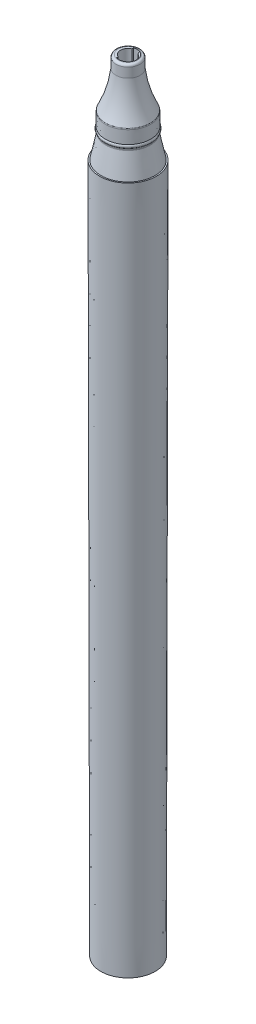
SolidWorks part; units mm, degrees
ref_plane "Plano frontal" through (0, 0, 0) normal (0, 0, 1) x (1, 0, 0)
ref_plane "Plano superior" through (0, 0, 0) normal (0, 1, 0) x (1, 0, 0)
ref_plane "Plano direito" through (0, 0, 0) normal (1, 0, 0) x (0, 0, -1)
sketch "Esboço1" plane through (0, 0, 0) normal (0, 0, 1) x (1, 0, 0)
  line L94 (3.75, 121.7) -> (3.7706, 119.7748) construction
  line L95 (4.275, 114.7) -> (4.5235, 0.7015)
  line L96 (3.8235, 0) -> (3.8021, 0)
  line L98 (2.01, 127.9) -> (2.01, 129.5)
  line L99 (1.61, 129.9) -> (1.5, 129.9)
  line L100 (3.825, 114.7) -> (4.275, 114.7)
  line L102 (0, 0) -> (0, 129.9) construction
  line L105 (2.3814, 122.73) -> (3.2071, 121.9043)
  line L110 (3.75, 121.7) -> (3.7706, 119.7748)
  line L117 (3.7852, 118.4178) -> (3.825, 114.7)
  line L119 (3.8235, 0) -> (3.8021, 0)
  line L123 (3.7764, 119.2315) -> (3.7852, 118.4178)
  line L124 (3.7764, 119.2315) -> (3.8229, 114.8979) construction
  line L152 (3.8021, 0.5) -> (3.8021, 0)
  line L153 (3.3527, 16.58) -> (3.2071, 121.9043)
  line L154 (3.4327, 11.1) -> (3.3677, 11.1)
  line L155 (3.4327, 8.5) -> (3.4327, 11.1)
  line L156 (3.3677, 8.5) -> (3.4327, 8.5)
  line L157 (3.3677, 5.8) -> (3.3677, 8.5)
  line L158 (3.4327, 5.8) -> (3.3677, 5.8)
  line L159 (3.4327, 3.2) -> (3.4327, 5.8)
  line L160 (3.3927, 3.2) -> (3.4327, 3.2)
  line L161 (3.3927, 0.5) -> (3.3927, 3.2)
  line L162 (3.3927, 0.5) -> (3.8021, 0.5)
  line L163 (3.3677, 11.1) -> (3.3527, 16.58)
  line L164 (33.3928, 114.7062) -> (34.2835, 114.7062)
  line L165 (31.5778, 127.9062) -> (31.5778, 129.5062)
  line L166 (31.1778, 129.9062) -> (31.0678, 129.9062)
  line L167 (29.5678, 129.9062) -> (29.5678, 114.7062) construction
  line L168 (29.5678, 0.0062) -> (29.5678, 129.9062) construction
  line L169 (32.0493, 122.6362) -> (32.7749, 121.9105)
  line L170 (33.3178, 121.7062) -> (33.3406, 119.5832)
  line L172 (31.0678, 129.9062) -> (31.0678, 127.9062)
  line L173 (34.0928, 0) -> (34.2835, 114.7062)
  line L174 (33.5193, 0.001) -> (34.0928, 0)
  line L175 (33.4928, 0.5062) -> (33.5193, 0.001)
  line L176 (32.8778, 16.5862) -> (32.7428, 114.2362)
  line L177 (32.9578, 11.1062) -> (32.8928, 11.1062)
  line L178 (32.9578, 8.5062) -> (32.9578, 11.1062)
  line L179 (32.8928, 8.5062) -> (32.9578, 8.5062)
  line L180 (32.8928, 5.8062) -> (32.8928, 8.5062)
  line L181 (32.9578, 5.8062) -> (32.8928, 5.8062)
  line L182 (32.9578, 3.2062) -> (32.9578, 5.8062)
  line L183 (32.9178, 3.2062) -> (32.9578, 3.2062)
  line L184 (32.9178, 0.5062) -> (32.9178, 3.2062)
  line L185 (32.9178, 0.5062) -> (33.4928, 0.5062)
  line L186 (32.8928, 11.1062) -> (32.8778, 16.5862)
  line L187 (56.8307, 127.9062) -> (56.8307, 129.5062)
  line L188 (56.4307, 129.9062) -> (56.3207, 129.9062)
  line L189 (54.8207, 129.9062) -> (54.8207, 114.7062) construction
  line L190 (54.8207, 0.0062) -> (54.8207, 129.9062) construction
  line L191 (57.3021, 122.6362) -> (58.0278, 121.9105)
  line L192 (58.5707, 121.7062) -> (58.5934, 119.5832)
  line L193 (56.3207, 129.9062) -> (56.3207, 127.9062)
  line L194 (59.3457, 0) -> (59.5364, 114.7062)
  line L195 (58.7722, 0.001) -> (59.3457, 0)
  line L196 (58.7457, 0.5062) -> (58.7722, 0.001)
  line L197 (58.1307, 16.5862) -> (57.9957, 114.2362)
  line L198 (58.2107, 11.1062) -> (58.1457, 11.1062)
  line L199 (58.2107, 8.5062) -> (58.2107, 11.1062)
  line L200 (58.1457, 8.5062) -> (58.2107, 8.5062)
  line L201 (58.1457, 5.8062) -> (58.1457, 8.5062)
  line L202 (58.2107, 5.8062) -> (58.1457, 5.8062)
  line L203 (58.2107, 3.2062) -> (58.2107, 5.8062)
  line L204 (58.1707, 3.2062) -> (58.2107, 3.2062)
  line L205 (58.1707, 0.5062) -> (58.1707, 3.2062)
  line L206 (58.1707, 0.5062) -> (58.7457, 0.5062)
  line L207 (58.1457, 11.1062) -> (58.1307, 16.5862)
  line L208 (58.4965, 118.7457) -> (59.091, 114.7062)
  line L209 (59.091, 114.7062) -> (59.5364, 114.7062)
  arc A9 (3.75, 121.7) -> (3.73, 121.9) centre (2.75, 121.701) ccw
  arc A10 (2.01, 127.9) -> (3.73, 121.9) centre (19.911, 129.7851) ccw
  arc A11 (2.01, 129.5) -> (1.61, 129.9) centre (1.61, 129.5) ccw
  arc A13 (3.7706, 119.7748) -> (3.7764, 119.2315) centre (3.48, 119.5) cw
  arc A14 (4.5235, 0.7015) -> (3.8235, 0) centre (3.8235, 0.7) cw
  arc A17 (33.3178, 121.7062) -> (33.2978, 121.9062) centre (32.3178, 121.7072) ccw
  arc A18 (31.5778, 127.9062) -> (33.2978, 121.9062) centre (49.4788, 129.7913) ccw
  arc A19 (31.5778, 129.5062) -> (31.1778, 129.9062) centre (31.1778, 129.5062) ccw
  arc A20 (31.9162, 122.8748) -> (32.0493, 122.6362) centre (32.4028, 122.9897) ccw
  arc A21 (33.3406, 119.5832) -> (33.3464, 119.0398) centre (33.0499, 119.3084) cw
  arc A22 (33.3464, 119.0398) -> (33.2436, 118.7457) centre (33.6428, 118.7713) ccw
  arc A23 (33.2436, 118.7457) -> (33.3928, 114.7062) centre (-41.6035, 113.9597) cw
  arc A24 (58.5707, 121.7062) -> (58.5507, 121.9062) centre (57.5707, 121.7072) ccw
  arc A25 (56.8307, 127.9062) -> (58.5507, 121.9062) centre (74.7317, 129.7913) ccw
  arc A26 (56.8307, 129.5062) -> (56.4307, 129.9062) centre (56.4307, 129.5062) ccw
  arc A27 (57.1691, 122.8748) -> (57.3021, 122.6362) centre (57.6557, 122.9897) ccw
  arc A28 (58.5934, 119.5832) -> (58.5993, 119.0398) centre (58.3028, 119.3084) cw
  arc A29 (58.5993, 119.0398) -> (58.4965, 118.7457) centre (58.8957, 118.7713) ccw
  spline S0 degree 3 poles (56.3207, 127.9062) (56.4125, 127.0377) (56.6457, 125.3307) (56.9781, 123.6834) (57.1691, 122.8748) knots 0 0 0 0 0.486102 0.972204 0.972204 0.972204 0.972204
  spline S1 degree 1 poles (57.9957, 114.2362) (58.0278, 121.9105) knots 0 0 1 1
  spline S2 degree 3 poles (1.5, 129.9) (1.512, 127.0428) (1.7225, 125.8207) (2.3814, 122.73) knots 0 0 0 0 1 1 1 1
  spline S3 degree 3 poles (31.0678, 127.9062) (31.1596, 127.0377) (31.3928, 125.3307) (31.7252, 123.6834) (31.9162, 122.8748) knots 0 0 0 0 0.486102 0.972204 0.972204 0.972204 0.972204
  spline S4 degree 1 poles (32.7428, 114.2362) (32.7749, 121.9105) knots 0 0 1 1
  point P5 (3.9157, 114.7013)
  point P60 (3.823, 118.6434)
  dimension "D4" = 0.7
revolve "Revolução1" add sketch "Esboço1" angle 360 about L168 region at (33.4455, 63.5049, 0)
ref_plane "Plano1" through (0, 129.9062, 0) normal (0, 1, 0) x (1, 0, 0)
sketch "Esboço3" plane through (0, 129.9062, 0) normal (0, 1, 0) x (1, 0, 0)
  line L0 (29.5678, 0) -> (29.5678, 1.475) construction
  line L1 (30.0678, -1.4142) -> (30.0678, -1.1456)
  line L2 (29.0678, -1.4142) -> (29.0678, -1.1456)
  line L3 (30.0678, 1.1456) -> (30.0678, 1.4142)
  line L4 (29.0678, 1.1456) -> (29.0678, 1.4142)
  arc A2 (30.0678, -1.4142) -> (30.0678, 1.4142) centre (29.5678, 0) ccw
  arc A3 (29.0678, 1.4142) -> (29.0678, -1.4142) centre (29.5678, 0) ccw
  arc A4 (29.0678, 1.1456) -> (29.0678, -1.1456) centre (29.5678, 0) ccw
  arc A5 (30.0678, -1.1456) -> (30.0678, 1.1456) centre (29.5678, 0) ccw
  dimension "D2" = 1
extrude "Ressalto-extrusão1" add sketch "Esboço3" against normal blind 2
chamfer "Chanfro1" distance 0.25 angle 45 1 edges at (30.8178, 129.9062, 0)
ref_plane "Plano2" through (0, -0.0075, 4.525) normal (0, -0.0017, 1) x (1, 0, 0)
surface "Superfície-Offset1" [suppressed] parameters "D1"=0.6213
sketch "Esboço4" plane through (-4.525, -0.0075, 4.525) normal (0, 0.0017, -1) x (-1, 0.0022, 0)
  line L269 (-36.2397, 60.3502) -> (-35.7318, 60.4878)
  line L290 (-36.0771, 61.607) -> (-35.164, 61.2311)
  line L292 (-35.6257, 58.7633) -> (-35.3131, 58.8744)
  line L293 (-35.3131, 58.8744) -> (-34.9187, 59.0128)
  line L294 (-36.4373, 58.751) -> (-36.6883, 58.6776)
  line L295 (-37.4772, 58.1398) -> (-37.3495, 58.194)
  line L299 (-34.3816, 55.3773) -> (-34.3567, 55.5991)
  line L300 (-34.6034, 55.6234) -> (-34.6177, 55.3965)
  line L301 (-34.6177, 55.3965) -> (-35.3424, 55.3673)
  line L302 (-35.7026, 55.3523) -> (-35.98, 55.3439)
  line L303 (-36.0671, 57.3017) -> (-36.0652, 57.3012)
  line L311 (-36.0378, 58.8744) -> (-35.7866, 58.9638)
  line L339 (-35.5806, 59.0371) -> (-34.7069, 59.348)
  line L398 (-34.0989, 66.5716) -> (-33.1235, 66.3749)
  line L399 (-34.0989, 66.4304) -> (-34.0989, 66.5716)
  line L400 (-34.8984, 66.6896) -> (-34.8984, 66.2002)
  line L401 (-33.1235, 67.3325) -> (-34.8984, 66.6896)
  line L402 (-33.1235, 67.7267) -> (-33.1235, 67.3325)
  line L403 (-35.0215, 67.0388) -> (-33.1235, 67.7267)
  line L404 (-35.0215, 65.843) -> (-35.0215, 67.0388)
  line L405 (-33.1235, 65.9372) -> (-34.0041, 66.1394)
  line L406 (-33.1235, 66.3749) -> (-33.1235, 65.9372)
  line L407 (-34.8482, 71.3355) -> (-33.1235, 71.9607)
  line L408 (-34.8482, 72.0642) -> (-34.8482, 71.3355)
  line L409 (-35.0195, 72.0022) -> (-34.8482, 72.0642)
  line L410 (-35.0195, 70.0576) -> (-35.0195, 72.0022)
  line L411 (-34.8482, 70.1195) -> (-35.0195, 70.0576)
  line L412 (-34.8482, 70.86) -> (-34.8482, 70.1195)
  line L413 (-33.1235, 71.4848) -> (-34.8482, 70.86)
  line L414 (-33.1235, 71.9607) -> (-33.1235, 71.4848)
  line L417 (-33.1166, 73.0058) -> (-33.3093, 72.9361)
  line L418 (-34.8274, 72.4975) -> (-35.0084, 72.432)
  line L420 (-33.5575, 75.1981) -> (-33.1235, 75.2063)
  line L421 (-33.5575, 76.0822) -> (-33.5575, 75.1981)
  line L422 (-33.1235, 76.3997) -> (-33.5575, 76.0822)
  line L423 (-33.1235, 76.5773) -> (-33.1235, 76.3997)
  line L424 (-34.8688, 75.2255) -> (-33.1235, 76.5773)
  line L425 (-33.1235, 74.7592) -> (-34.9153, 74.8236)
  line L426 (-33.1235, 75.2063) -> (-33.1235, 74.7592)
  line L427 (-34.0026, 77.2834) -> (-34.0026, 76.9922)
  line L428 (-34.0989, 77.298) -> (-34.0026, 77.2834)
  line L429 (-34.0989, 77.1527) -> (-34.0989, 77.298)
  line L430 (-34.8984, 77.4109) -> (-34.8984, 76.9224)
  line L431 (-33.1235, 78.0541) -> (-34.8984, 77.4109)
  line L432 (-33.1235, 78.4489) -> (-33.1235, 78.0541)
  line L433 (-35.0215, 77.761) -> (-33.1235, 78.4489)
  line L434 (-35.0215, 76.5649) -> (-35.0215, 77.761)
  line L435 (-34.8916, 80.5362) -> (-33.1235, 81.1764)
  line L436 (-33.7285, 79.9353) -> (-34.9019, 80.1736)
  line L437 (-34.8645, 78.8523) -> (-33.7285, 79.9353)
  line L438 (-33.1235, 78.9837) -> (-34.8456, 78.3594)
  line L439 (-33.1235, 79.417) -> (-33.1235, 78.9837)
  line L440 (-34.6144, 78.8764) -> (-33.1235, 79.417)
  line L441 (-33.208, 80.2223) -> (-34.6144, 78.8764)
  line L442 (-34.5506, 80.5078) -> (-33.208, 80.2223)
  line L443 (-33.1235, 81.0251) -> (-34.5506, 80.5078)
  line L444 (-33.1235, 81.1764) -> (-33.1235, 81.0251)
  line L445 (-34.7968, 75.1753) -> (-33.6815, 75.1955)
  line L446 (-33.6815, 75.9913) -> (-34.7968, 75.1753)
  line L447 (-33.6815, 75.1955) -> (-33.6815, 75.9913)
  line L448 (-34.8274, 83.5514) -> (-35.0084, 83.4854)
  line L449 (-33.1166, 84.0596) -> (-33.3093, 83.99)
  line L450 (-35.8251, 57.2389) -> (-35.6684, 57.1983)
  line L451 (-35.836, 58.7118) -> (-36.0278, 57.5285)
  line L452 (-36.2903, 55.3344) -> (-37.3146, 55.3031)
  line L468 (-32.5455, 57.3866) -> (-32.2568, 57.4648)
  line L469 (-32.3829, 58.6433) -> (-32.1608, 58.5519)
  line L472 (-33.4428, 56.2803) -> (-33.4378, 56.5071)
  line L473 (-33.9956, 54.2346) -> (-34.0348, 54.052)
  line L474 (-32.5755, 52.107) -> (-32.7824, 52.1362)
  line L475 (-32.8173, 53.1519) -> (-32.654, 53.1369)
  line L476 (-32.5163, 52.7674) -> (-32.7331, 52.7232)
  line L477 (-31.8852, 58.4385) -> (-31.4022, 58.2396)
  line L478 (-37.0977, 62.4401) -> (-37.0919, 62.4401)
  line L479 (-31.0912, 50.0606) -> (-31.0987, 50.0606)
  ellipse E0 centre (-34.1678, 52.3807) end of major axis (-34.1678, 42.412) minor radius 1.898 (-35.6257, 58.7633) -> (-35.7985, 57.4811) ccw
  ellipse E1 centre (-34.1678, 52.3807) end of major axis (-34.1678, 42.412) minor radius 1.898 (-35.8251, 57.2389) -> (-35.98, 55.3439) ccw
  ellipse E2 centre (-34.1678, 52.3807) end of major axis (-34.1678, 42.412) minor radius 1.898 (-35.9933, 55.1091) -> (-36.0544, 51.2886) ccw
  ellipse E3 centre (-34.1678, 52.3807) end of major axis (-34.1678, 42.412) minor radius 1.898 (-35.0573, 61.1869) -> (-35.1683, 60.852) ccw
  ellipse E4 centre (-34.1678, 52.3807) end of major axis (-34.1678, 42.412) minor radius 1.898 (-35.2358, 60.6212) -> (-35.5806, 59.0371) ccw
  ellipse E5 centre (-33.9277, 62.1927) end of major axis (-33.9277, 52.224) minor radius 1.898 (-33.0302, 53.4089) -> (-32.4579, 55.8854) ccw
  ellipse E6 centre (-33.9277, 62.1927) end of major axis (-33.9277, 52.224) minor radius 1.898 (-33.4782, 52.5077) -> (-33.1148, 53.1847) ccw
  ellipse E7 centre (-33.9277, 62.1927) end of major axis (-33.9277, 52.224) minor radius 1.898 (-32.4221, 56.1229) -> (-32.2568, 57.4648) ccw
  ellipse E8 centre (-33.9277, 62.1927) end of major axis (-33.9277, 52.224) minor radius 1.898 (-32.2337, 57.6973) -> (-32.1608, 58.5519) ccw
  ellipse E9 centre (-33.9277, 62.1927) end of major axis (-33.9277, 52.224) minor radius 1.898 (-32.1422, 58.8123) -> (-32.039, 61.2082) ccw
  spline S0 degree 3 poles (-37.2604, 60.0292) (-37.2097, 60.0529) (-37.1272, 60.0878) (-37.0075, 60.1282) (-36.921, 60.1563) (-36.8437, 60.1781) (-36.778, 60.1975) (-36.7053, 60.219) (-36.6256, 60.2417) (-36.539, 60.2659) (-36.4097, 60.3025) (-36.3093, 60.3312) (-36.2397, 60.3502) knots 0 0 0 0 0.156743 0.250465 0.35388 0.41142 0.475274 0.54608 0.623654 0.707357 0.798013 1 1 1 1
  spline S1 degree 3 poles (-35.7318, 60.4878) (-35.618, 60.5189) (-35.5041, 60.5502) (-35.3901, 60.5806) knots 0 0 0 0 0.267416 0.267416 0.267416 0.267416
  spline S2 degree 3 poles (-34.4451, 60.7988) (-34.4182, 60.8032) (-34.3788, 60.8163) (-34.3335, 60.8474) (-34.3031, 60.8769) (-34.2775, 60.9136) (-34.2535, 60.978) (-34.2483, 61.032) (-34.2482, 61.0699) knots 0 0 0 0 0.221546 0.331484 0.444969 0.564565 0.691309 1 1 1 1
  spline S3 degree 3 poles (-34.2482, 61.0699) (-34.253, 61.0818) (-34.2754, 61.0941) (-34.3103, 61.1163) (-34.3566, 61.1389) (-34.415, 61.1678) (-34.4867, 61.2009) (-34.5714, 61.2388) (-34.6681, 61.2813) (-34.7762, 61.3269) (-34.8781, 61.3717) (-34.9444, 61.3997) (-34.9908, 61.4193) (-35.01, 61.4274) (-35.0292, 61.4355) knots 0 0 0 0 0.021724 0.044055 0.074695 0.113518 0.160922 0.215965 0.279608 0.349953 0.425997 0.478788 0.478788 0.516099 0.516099 0.516099 0.516099
  spline S4 degree 3 poles (-35.7768, 61.7503) (-35.9111, 61.8074) (-36.1075, 61.8969) (-36.3645, 62.0173) (-36.5157, 62.0942) (-36.6297, 62.1521) (-36.7048, 62.1923) (-36.7705, 62.2284) (-36.8266, 62.2615) (-36.8742, 62.2893) (-36.9181, 62.3202) (-36.9464, 62.3415) (-36.9601, 62.3566) knots 0 0 0 0 0.328466 0.486 0.638711 0.710283 0.773975 0.830275 0.879203 0.920509 0.95436 1 1 1 1
  spline S5 degree 3 poles (-36.9601, 62.3566) (-36.9784, 62.3809) (-37.018, 62.422) (-37.0723, 62.4407) (-37.0977, 62.4401) knots 0 0 0 0 0.550104 1 1 1 1
  spline S6 degree 3 poles (-37.0977, 62.4401) (-37.1128, 62.439) (-37.1361, 62.4271) (-37.1657, 62.4016) (-37.1921, 62.3737) (-37.217, 62.3419) (-37.2418, 62.2978) (-37.2508, 62.2619) (-37.2504, 62.2382) knots 0 0 0 0 0.165063 0.285997 0.436553 0.594071 0.736979 1 1 1 1
  spline S7 degree 3 poles (-37.2504, 62.2382) (-37.252, 62.2164) (-37.2393, 62.1615) (-37.1864, 62.1392) (-37.1669, 62.1198) knots 0 0 0 0 0.436321 1 1 1 1
  spline S8 degree 3 poles (-37.1669, 62.1198) (-37.1471, 62.1069) (-37.1135, 62.0865) (-37.0638, 62.0586) (-37.0164, 62.0337) (-36.9621, 62.0059) (-36.9011, 61.9753) (-36.833, 61.9425) (-36.7324, 61.8945) (-36.5985, 61.8323) (-36.3711, 61.7311) (-36.1964, 61.656) (-36.0771, 61.607) knots 0 0 0 0 0.058964 0.097641 0.141844 0.192388 0.249279 0.311733 0.380544 0.526672 0.678967 1 1 1 1
  spline S9 degree 3 poles (-35.0573, 61.1869) (-35.0343, 61.1772) (-34.9797, 61.1538) (-34.8971, 61.1183) (-34.8125, 61.0838) (-34.7403, 61.0528) (-34.6791, 61.0281) (-34.622, 61.0036) (-34.5845, 60.9888) (-34.5635, 60.9807) knots 0.073318 0.073318 0.073318 0.073318 0.202582 0.382457 0.540282 0.677014 0.790562 0.883015 1 1 1 1
  spline S10 degree 3 poles (-34.5635, 60.9807) (-34.5845, 60.9785) (-34.62, 60.9727) (-34.6727, 60.9631) (-34.7244, 60.9535) (-34.7836, 60.94) (-34.8511, 60.9262) (-34.9263, 60.9087) (-35.0331, 60.8843) (-35.1146, 60.8648) (-35.1683, 60.852) knots 0 0 0 0 0.050143 0.085077 0.12697 0.174836 0.229001 0.290255 0.35793 0.48875 0.48875 0.48875 0.48875
  spline S11 degree 3 poles (-35.796, 60.6954) (-35.8966, 60.6697) (-36.0428, 60.6297) (-36.2327, 60.5795) (-36.3622, 60.5433) (-36.4838, 60.511) (-36.5963, 60.4793) (-36.7008, 60.4502) (-36.8257, 60.4139) (-36.9683, 60.3723) (-37.1635, 60.3069) (-37.3007, 60.2587) (-37.3838, 60.2218) knots 0 0 0 0 0.187827 0.274231 0.355427 0.43119 0.501747 0.566985 0.627436 0.737 0.835765 1 1 1 1
  spline S12 degree 3 poles (-37.3838, 60.2218) (-37.439, 60.1987) (-37.513, 60.1631) (-37.5994, 60.1139) (-37.6433, 60.0823) (-37.6747, 60.0501) (-37.7052, 60.0079) (-37.714, 59.9701) (-37.714, 59.9458) knots 0 0 0 0 0.39628 0.542249 0.658037 0.752599 0.838565 1 1 1 1
  spline S13 degree 3 poles (-37.714, 59.9458) (-37.7122, 59.9326) (-37.6963, 59.9145) (-37.6694, 59.8889) (-37.6376, 59.8664) (-37.6054, 59.8444) (-37.5725, 59.8242) (-37.5499, 59.8139) (-37.5364, 59.8124) knots 0 0 0 0 0.166588 0.308352 0.491833 0.676803 0.822859 1 1 1 1
  spline S14 degree 3 poles (-37.5364, 59.8124) (-37.5249, 59.8159) (-37.5079, 59.8322) (-37.4803, 59.8592) (-37.451, 59.8936) (-37.4146, 59.9316) (-37.3525, 59.9812) (-37.2984, 60.0108) (-37.2604, 60.0292) knots 0 0 0 0 0.099102 0.195949 0.328593 0.480992 0.641418 1 1 1 1
  spline S15 degree 3 poles (-35.9933, 55.1091) (-35.953, 55.1101) (-35.8368, 55.1129) (-35.65, 55.1166) (-35.4387, 55.1222) (-35.2435, 55.1252) (-35.0649, 55.1291) (-34.8598, 55.1326) (-34.7142, 55.1347) (-34.6227, 55.1355) knots 0.495605 0.495605 0.495605 0.495605 0.540122 0.623861 0.701827 0.773484 0.83937 0.898952 1 1 1 1
  spline S16 degree 3 poles (-36.0652, 57.3012) (-36.1139, 56.9538) (-36.1948, 56.3103) (-36.2628, 55.6367) (-36.2903, 55.3344) knots 1.058307 1.058307 1.058307 1.058307 1.178097 1.273083 1.273083 1.273083 1.273083
  spline S17 degree 3 poles (-35.6684, 57.1983) (-35.6199, 57.1841) (-35.5065, 57.1592) (-35.393, 57.1349) (-35.3281, 57.1241) knots 0 0 0 0 0.434134 1 1 1 1
  spline S18 degree 3 poles (-35.3281, 57.1241) (-35.1738, 57.0977) (-34.8902, 57.0412) (-34.6082, 56.9767) (-34.48, 56.9422) knots 0 0 0 0 0.541127 1 1 1 1
  spline S19 degree 3 poles (-34.48, 56.9422) (-34.4502, 56.9355) (-34.4058, 56.9269) (-34.3614, 56.9178) (-34.3467, 56.9172) knots 0 0 0 0 0.675822 1 1 1 1
  spline S20 degree 3 poles (-34.3467, 56.9172) (-34.3308, 56.9164) (-34.3075, 56.9225) (-34.2798, 56.939) (-34.2439, 56.9745) (-34.2268, 57.0162) (-34.2283, 57.0506) knots 0 0 0 0 0.238518 0.356844 0.487136 1 1 1 1
  spline S21 degree 3 poles (-34.2283, 57.0506) (-34.2285, 57.0669) (-34.2358, 57.092) (-34.2573, 57.1203) (-34.2989, 57.1563) (-34.3391, 57.1788) (-34.3716, 57.1933) knots 0 0 0 0 0.227846 0.35722 0.497227 1 1 1 1
  spline S22 degree 3 poles (-34.3716, 57.1933) (-34.4953, 57.2253) (-34.6564, 57.259) (-34.8583, 57.2946) (-35.0243, 57.3228) (-35.1538, 57.3469) (-35.244, 57.3609) knots 0 0 0 0 0.431328 0.555254 0.692109 1 1 1 1
  spline S23 degree 3 poles (-35.244, 57.3609) (-35.2921, 57.3688) (-35.368, 57.3816) (-35.4737, 57.4049) (-35.5606, 57.4248) (-35.6436, 57.4433) (-35.7137, 57.4611) (-35.7636, 57.4727) (-35.7901, 57.4791) (-35.7985, 57.4811) knots 0 0 0 0 0.252127 0.397934 0.559199 0.713003 0.836978 0.932946 0.977844 0.977844 0.977844 0.977844
  spline S24 degree 3 poles (-33.5662, 57.0656) (-33.5155, 57.0893) (-33.4331, 57.1242) (-33.3134, 57.1646) (-33.2269, 57.1927) (-33.1496, 57.2144) (-33.0838, 57.2339) (-33.0112, 57.2554) (-32.9315, 57.2781) (-32.8449, 57.3023) (-32.7156, 57.3388) (-32.6151, 57.3676) (-32.5455, 57.3866) knots 0 0 0 0 0.156743 0.250465 0.35388 0.41142 0.475274 0.54608 0.623654 0.707357 0.798013 1 1 1 1
  spline S25 degree 3 poles (-34.9187, 59.0128) (-34.8343, 59.0393) (-34.712, 59.079) (-34.553, 59.1268) (-34.446, 59.1597) (-34.3464, 59.1893) (-34.2288, 59.2216) (-34.1446, 59.2455) (-34.0906, 59.2589) knots 0 0 0 0 0.307305 0.446235 0.576547 0.696184 0.806747 1 1 1 1
  spline S26 degree 3 poles (-34.0906, 59.2589) (-34.0485, 59.2682) (-33.9954, 59.2916) (-33.954, 59.3408) (-33.9328, 59.3756) (-33.9282, 59.4065) (-33.928, 59.4265) knots 0 0 0 0 0.520848 0.6429 0.760436 1 1 1 1
  spline S27 degree 3 poles (-33.928, 59.4265) (-33.9269, 59.4589) (-33.9393, 59.5002) (-33.9729, 59.5351) (-34.001, 59.5505) (-34.0249, 59.5557) (-34.0414, 59.5549) knots 0 0 0 0 0.50556 0.626052 0.745516 1 1 1 1
  spline S28 degree 3 poles (-34.0414, 59.5549) (-34.0701, 59.5542) (-34.1199, 59.5419) (-34.1958, 59.5202) (-34.27, 59.4959) (-34.3431, 59.4712) (-34.4128, 59.4477) (-34.4565, 59.4331) (-34.48, 59.4265) knots 0 0 0 0 0.187055 0.334476 0.517727 0.698505 0.839877 1 1 1 1
  spline S29 degree 3 poles (-34.48, 59.4265) (-34.507, 59.4163) (-34.5824, 59.3896) (-34.6584, 59.3644) (-34.7069, 59.348) knots 0 0 0 0 0.360029 1 1 1 1
  spline S30 degree 3 poles (-35.0182, 61.4308) (-35.0359, 61.4383) (-35.0536, 61.4458) (-35.098, 61.4646) (-35.1724, 61.4961) (-35.2975, 61.5489) (-35.5057, 61.6373) (-35.6669, 61.7036) (-35.7768, 61.7503) knots 0.508955 0.508955 0.508955 0.508955 0.543363 0.543363 0.595129 0.687992 0.786387 1 1 1 1
  spline S31 degree 3 poles (-35.164, 61.2311) (-35.215, 61.1021) (-35.2653, 60.9639) (-35.3144, 60.8168) knots 6.772543 6.772543 6.772543 6.772543 6.853641 6.853641 6.853641 6.853641
  spline S32 degree 3 poles (-35.3144, 60.8168) (-35.3361, 60.8116) (-35.497, 60.7724) (-35.6573, 60.7312) (-35.796, 60.6954) knots 0.607549 0.607549 0.607549 0.607549 0.660449 1 1 1 1
  spline S33 degree 3 poles (-35.2358, 60.6212) (-35.1984, 60.6309) (-35.1047, 60.6547) (-34.9599, 60.6898) (-34.8077, 60.7266) (-34.6383, 60.7643) (-34.5191, 60.7867) (-34.4451, 60.7988) knots 0.387827 0.387827 0.387827 0.387827 0.475422 0.606836 0.725324 0.830128 1 1 1 1
  spline S34 degree 3 poles (-35.3901, 60.5806) (-35.4923, 60.2476) (-35.6278, 59.7265) (-35.7522, 59.1369) (-35.7866, 58.9638) knots 6.895728 6.895728 6.895728 6.895728 7.068583 7.137432 7.137432 7.137432 7.137432
  spline S35 degree 3 poles (-31.9943, 57.5361) (-31.9356, 57.5521) (-31.8094, 57.5866) (-31.6212, 57.6372) (-31.4353, 57.6851) (-31.2658, 57.7262) (-31.1136, 57.7629) (-30.9442, 57.8006) (-30.825, 57.8231) (-30.751, 57.8352) knots 0.03396 0.03396 0.03396 0.03396 0.171947 0.33029 0.475422 0.606836 0.725324 0.830128 1 1 1 1
  spline S36 degree 3 poles (-30.751, 57.8352) (-30.7241, 57.8396) (-30.6847, 57.8527) (-30.6393, 57.8838) (-30.6089, 57.9133) (-30.5834, 57.9499) (-30.5593, 58.0144) (-30.5541, 58.0684) (-30.5541, 58.1062) knots 0 0 0 0 0.221546 0.331484 0.444969 0.564565 0.691309 1 1 1 1
  spline S37 degree 3 poles (-36.0378, 58.8744) (-36.0913, 58.858) (-36.1614, 58.8345) (-36.2508, 58.8061) (-36.3304, 58.781) (-36.3934, 58.7632) (-36.4373, 58.751) knots 0 0 0 0 0.401398 0.530343 0.67333 1 1 1 1
  spline S38 degree 3 poles (-36.6883, 58.6776) (-36.787, 58.6504) (-36.9252, 58.6096) (-37.0986, 58.5611) (-37.2015, 58.5306) (-37.2874, 58.5069) (-37.3658, 58.4835) (-37.4157, 58.4687) (-37.443, 58.46) knots 0 0 0 0 0.39096 0.550512 0.687611 0.800882 0.890828 1 1 1 1
  spline S39 degree 3 poles (-37.443, 58.46) (-37.4796, 58.4462) (-37.5242, 58.4317) (-37.5686, 58.4028) (-37.5854, 58.3829) (-37.5914, 58.3643) (-37.5906, 58.3516) knots 0 0 0 0 0.604601 0.712046 0.807938 1 1 1 1
  spline S40 degree 2 poles (-37.5906, 58.3516) (-37.5922, 58.2604) (-37.5614, 58.1747) knots 0 0 0 1 1 1
  spline S41 degree 3 poles (-37.5614, 58.1747) (-37.5745, 58.1631) (-37.5988, 58.1464) (-37.6298, 58.1209) (-37.6563, 58.0815) (-37.6604, 58.0453) (-37.6598, 58.0214) knots 0 0 0 0 0.271947 0.460801 0.621049 1 1 1 1
  spline S42 degree 3 poles (-37.6598, 58.0214) (-37.6608, 58.0049) (-37.651, 57.9806) (-37.6308, 57.9497) (-37.6087, 57.9241) (-37.5796, 57.8985) (-37.5443, 57.8725) (-37.5036, 57.8442) (-37.4386, 57.8064) (-37.3499, 57.7575) (-37.1914, 57.6805) (-37.0663, 57.627) (-36.9793, 57.5927) knots 0 0 0 0 0.057988 0.092946 0.133955 0.180409 0.23341 0.293028 0.360386 0.506024 0.66083 1 1 1 1
  spline S43 degree 3 poles (-36.9793, 57.5927) (-36.9125, 57.5665) (-36.8012, 57.5273) (-36.6387, 57.4749) (-36.5184, 57.4376) (-36.4187, 57.4071) (-36.3483, 57.3859) (-36.2848, 57.3666) (-36.2283, 57.3494) (-36.1784, 57.3344) (-36.1351, 57.3216) (-36.0987, 57.3109) (-36.0768, 57.3045) (-36.0671, 57.3017) knots 0 0 0 0 0.224741 0.369576 0.534927 0.619026 0.696062 0.765323 0.82681 0.881234 0.928598 0.968186 1 1 1 1
  spline S44 degree 3 poles (-30.5541, 58.1062) (-30.5589, 58.1181) (-30.5813, 58.1305) (-30.6161, 58.1527) (-30.6624, 58.1753) (-30.7209, 58.2042) (-30.7926, 58.2373) (-30.8773, 58.2752) (-30.974, 58.3177) (-31.0821, 58.3633) (-31.1989, 58.4146) (-31.3252, 58.4676) (-31.4599, 58.5248) (-31.6033, 58.5853) (-31.7369, 58.642) (-31.8229, 58.6779) (-31.8582, 58.6926) knots 0 0 0 0 0.021724 0.044055 0.074695 0.113518 0.160922 0.215965 0.279608 0.349953 0.425997 0.507797 0.595129 0.687992 0.786387 0.854815 0.854815 0.854815 0.854815
  spline S45 degree 3 poles (-32.1422, 58.8123) (-32.1903, 58.8331) (-32.3039, 58.8835) (-32.4804, 58.9647) (-32.6704, 59.0536) (-32.8215, 59.1306) (-32.9356, 59.1885) (-33.0106, 59.2287) (-33.0764, 59.2648) (-33.1325, 59.2979) (-33.1801, 59.3257) (-33.224, 59.3566) (-33.2523, 59.3778) (-33.2659, 59.393) knots 0.048618 0.048618 0.048618 0.048618 0.166565 0.328466 0.486 0.638711 0.710283 0.773975 0.830275 0.879203 0.920509 0.95436 1 1 1 1
  spline S46 degree 3 poles (-33.2659, 59.393) (-33.2842, 59.4172) (-33.3239, 59.4584) (-33.3782, 59.4771) (-33.4036, 59.4764) knots 0 0 0 0 0.550104 1 1 1 1
  spline S47 degree 3 poles (-33.4036, 59.4764) (-33.4186, 59.4753) (-33.442, 59.4635) (-33.4716, 59.438) (-33.4979, 59.41) (-33.5228, 59.3782) (-33.5477, 59.3342) (-33.5567, 59.2983) (-33.5562, 59.2746) knots 0 0 0 0 0.165063 0.285997 0.436553 0.594071 0.736979 1 1 1 1
  spline S48 degree 3 poles (-36.8609, 57.7803) (-36.9901, 57.8294) (-37.1459, 57.9034) (-37.3182, 58.0055) (-37.4026, 58.0621) (-37.4542, 58.1071) (-37.4772, 58.1398) knots 0 0 0 0 0.576071 0.717023 0.834718 1 1 1 1
  spline S49 degree 3 poles (-37.3495, 58.194) (-37.2909, 58.2238) (-37.179, 58.2755) (-37.0638, 58.3192) (-37.0093, 58.3373) knots 0 0 0 0 0.533838 1 1 1 1
  spline S50 degree 3 poles (-37.0093, 58.3373) (-36.9402, 58.3594) (-36.8301, 58.3968) (-36.6727, 58.4463) (-36.5338, 58.4919) (-36.3796, 58.5397) (-36.1457, 58.6147) (-35.9627, 58.672) (-35.836, 58.7118) knots 0 0 0 0 0.176726 0.283134 0.40181 0.532952 0.67636 1 1 1 1
  spline S51 degree 3 poles (-36.0278, 57.5285) (-36.0468, 57.534) (-36.0784, 57.542) (-36.1241, 57.5556) (-36.1676, 57.5677) (-36.2174, 57.5809) (-36.2729, 57.5969) (-36.3346, 57.6139) (-36.4225, 57.6391) (-36.5312, 57.6693) (-36.6852, 57.7173) (-36.7936, 57.7545) (-36.8609, 57.7803) knots 0 0 0 0 0.067973 0.112311 0.164189 0.223612 0.290006 0.363153 0.444064 0.605098 0.751763 1 1 1 1
  spline S52 degree 3 poles (-37.4629, 54.0513) (-37.4476, 54.1272) (-37.4279, 54.2487) (-37.4035, 54.4199) (-37.3856, 54.5638) (-37.3699, 54.7068) (-37.3524, 54.874) (-37.3433, 54.9922) (-37.3395, 55.0663) knots 0 0 0 0 0.227076 0.360872 0.507014 0.65222 0.782571 1 1 1 1
  spline S53 degree 3 poles (-37.3395, 55.0663) (-37.3177, 55.0686) (-37.2818, 55.0692) (-37.2299, 55.0722) (-37.1817, 55.0743) (-37.1272, 55.0762) (-37.0664, 55.0795) (-36.9993, 55.0813) (-36.9261, 55.0833) (-36.8464, 55.0864) (-36.7606, 55.0894) (-36.6686, 55.0911) (-36.5704, 55.0943) (-36.466, 55.0971) (-36.3787, 55.0991) (-36.3264, 55.1008) (-36.3109, 55.1012) knots 0 0 0 0 0.024183 0.039687 0.057288 0.077511 0.099843 0.124525 0.151568 0.180718 0.21249 0.246354 0.282323 0.320916 0.361607 0.378697 0.378697 0.378697 0.378697
  spline S54 degree 3 poles (-34.6227, 55.1355) (-34.625, 55.0327) (-34.6344, 54.7994) (-34.6482, 54.5662) (-34.6577, 54.4358) knots 0 0 0 0 0.440093 1 1 1 1
  spline S55 degree 3 poles (-34.6577, 54.4358) (-34.6595, 54.3815) (-34.6653, 54.3053) (-34.6687, 54.2101) (-34.6718, 54.154) (-34.6741, 54.1079) (-34.6752, 54.0665) (-34.6775, 54.0404) (-34.6769, 54.0264) knots 0 0 0 0 0.397301 0.559283 0.69693 0.808421 0.897236 1 1 1 1
  spline S56 degree 3 poles (-34.6769, 54.0264) (-34.678, 53.9979) (-34.6717, 53.9561) (-34.6559, 53.9029) (-34.6388, 53.8667) (-34.6175, 53.8344) (-34.5776, 53.8025) (-34.5395, 53.7938) (-34.5143, 53.7945) knots 0 0 0 0 0.268223 0.397842 0.524753 0.645943 0.761282 1 1 1 1
  spline S57 degree 3 poles (-34.5143, 53.7945) (-34.4943, 53.794) (-34.4667, 53.7972) (-34.4331, 53.8052) (-34.4146, 53.8157) (-34.4007, 53.8313) (-34.3871, 53.8637) (-34.3873, 53.8926) (-34.3859, 53.9129) knots 0 0 0 0 0.288035 0.402681 0.498508 0.591309 0.700916 1 1 1 1
  spline S58 degree 3 poles (-34.3859, 53.9129) (-34.3859, 53.9313) (-34.391, 53.9856) (-34.3971, 54.0397) (-34.4009, 54.0756) knots 0 0 0 0 0.337012 1 1 1 1
  spline S59 degree 2 poles (-34.4009, 54.0756) (-34.419, 54.1584) (-34.4208, 54.2432) knots 0 0 0 1 1 1
  spline S60 degree 3 poles (-34.4208, 54.2432) (-34.4205, 54.2915) (-34.4192, 54.3711) (-34.4165, 54.4869) (-34.4138, 54.5956) (-34.4095, 54.7187) (-34.4008, 54.912) (-34.3963, 55.0642) (-34.3909, 55.1704) knots 0 0 0 0 0.156083 0.257589 0.374486 0.507567 0.656071 1 1 1 1
  spline S61 degree 3 poles (-34.3909, 55.1704) (-34.3697, 55.185) (-34.3384, 55.2196) (-34.3228, 55.2636) (-34.3224, 55.2838) knots 0 0 0 0 0.561073 1 1 1 1
  spline S62 degree 3 poles (-34.3224, 55.2838) (-34.3234, 55.304) (-34.3301, 55.3448) (-34.3611, 55.3748) (-34.3816, 55.3773) knots 0 0 0 0 0.513018 1 1 1 1
  spline S63 degree 3 poles (-34.3567, 55.5991) (-34.3491, 55.659) (-34.3386, 55.7457) (-34.3268, 55.8575) (-34.3193, 55.9321) (-34.3149, 56.0007) (-34.3087, 56.0795) (-34.3077, 56.1357) (-34.3074, 56.1712) knots 0 0 0 0 0.315093 0.456182 0.587139 0.706648 0.814923 1 1 1 1
  spline S64 degree 3 poles (-34.3074, 56.1712) (-34.3078, 56.2189) (-34.3144, 56.3069) (-34.352, 56.387) (-34.3766, 56.4172) knots 0 0 0 0 0.553015 1 1 1 1
  spline S65 degree 3 poles (-34.3766, 56.4172) (-34.3912, 56.4342) (-34.4386, 56.4564) (-34.4899, 56.4618) (-34.5193, 56.4615) knots 0 0 0 0 0.425712 1 1 1 1
  spline S66 degree 3 poles (-34.5193, 56.4615) (-34.5473, 56.4595) (-34.5954, 56.4331) (-34.6372, 56.3934) (-34.6377, 56.363) knots 0 0 0 0 0.495829 1 1 1 1
  spline S67 degree 3 poles (-34.6377, 56.363) (-34.6369, 56.3546) (-34.6316, 56.3391) (-34.6217, 56.314) (-34.5978, 56.2572) (-34.5839, 56.2045) (-34.5835, 56.1612) knots 0 0 0 0 0.119661 0.232497 0.386299 1 1 1 1
  spline S68 degree 3 poles (-34.5835, 56.1612) (-34.584, 56.0858) (-34.588, 55.9064) (-34.5982, 55.7272) (-34.6034, 55.6234) knots 0 0 0 0 0.420208 1 1 1 1
  spline S69 degree 3 poles (-35.3424, 55.3673) (-35.4107, 55.3647) (-35.5306, 55.3576) (-35.6507, 55.3526) (-35.7026, 55.3523) knots 0 0 0 0 0.568468 1 1 1 1
  spline S70 degree 3 poles (-37.3146, 55.3031) (-37.3104, 55.3773) (-37.3022, 55.4802) (-37.2946, 55.6063) (-37.2888, 55.6756) (-37.2865, 55.7284) (-37.2816, 55.7646) (-37.2829, 55.7842) (-37.2803, 55.791) knots 0 0 0 0 0.455982 0.632806 0.774617 0.882768 0.95591 1 1 1 1
  spline S71 degree 3 poles (-37.2803, 55.791) (-37.2739, 55.8661) (-37.267, 55.9724) (-37.256, 56.1055) (-37.2514, 56.1861) (-37.2473, 56.2537) (-37.2423, 56.3178) (-37.2418, 56.3595) (-37.2411, 56.383) knots 0 0 0 0 0.380944 0.538872 0.674964 0.789387 0.880941 1 1 1 1
  spline S72 degree 3 poles (-37.2411, 56.383) (-37.2415, 56.4105) (-37.2477, 56.4525) (-37.2715, 56.5039) (-37.2939, 56.5412) (-37.3228, 56.5727) (-37.3661, 56.6062) (-37.407, 56.6141) (-37.433, 56.6148) knots 0 0 0 0 0.249327 0.376408 0.510672 0.641589 0.761594 1 1 1 1
  spline S73 degree 3 poles (-37.433, 56.6148) (-37.4661, 56.6165) (-37.5098, 56.603) (-37.5422, 56.5658) (-37.558, 56.5377) (-37.5613, 56.5128) (-37.5614, 56.4964) knots 0 0 0 0 0.512348 0.628078 0.748272 1 1 1 1
  spline S74 degree 3 poles (-37.5614, 56.4964) (-37.5613, 56.4702) (-37.5573, 56.4174) (-37.5495, 56.3652) (-37.5464, 56.3388) knots 0 0 0 0 0.496362 1 1 1 1
  spline S75 degree 2 poles (-37.5464, 56.3388) (-37.5225, 56.2216) (-37.5214, 56.102) knots 0 0 0 1 1 1
  spline S76 degree 3 poles (-37.5214, 56.102) (-37.5204, 56.0798) (-37.5234, 56.0435) (-37.5231, 55.9909) (-37.5261, 55.9422) (-37.5274, 55.8875) (-37.532, 55.8267) (-37.5339, 55.7596) (-37.5386, 55.6883) (-37.5428, 55.617) (-37.5462, 55.5499) (-37.5496, 55.4892) (-37.5537, 55.4351) (-37.5555, 55.387) (-37.558, 55.3357) (-37.5606, 55.3003) (-37.5614, 55.2789) knots 0 0 0 0 0.08052 0.132453 0.191361 0.25805 0.33174 0.413165 0.502456 0.591748 0.673214 0.746904 0.812819 0.870862 0.921989 1 1 1 1
  spline S77 degree 3 poles (-37.5614, 55.2789) (-37.6002, 55.2771) (-37.6478, 55.2573) (-37.6865, 55.214) (-37.7037, 55.1792) (-37.7091, 55.1502) (-37.709, 55.1305) knots 0 0 0 0 0.501759 0.624005 0.745199 1 1 1 1
  spline S78 degree 3 poles (-37.709, 55.1305) (-37.7083, 55.1059) (-37.6635, 55.071) (-37.6117, 55.0615) (-37.5806, 55.0613) knots 0 0 0 0 0.416026 1 1 1 1
  spline S79 degree 3 poles (-37.5806, 55.0613) (-37.5826, 55.0041) (-37.5905, 54.9111) (-37.6035, 54.7778) (-37.6181, 54.6561) (-37.6358, 54.5203) (-37.6663, 54.3104) (-37.6904, 54.1458) (-37.709, 54.0314) knots 0 0 0 0 0.165289 0.269522 0.387101 0.519419 0.665133 1 1 1 1
  spline S80 degree 3 poles (-37.709, 54.0314) (-37.7168, 53.9839) (-37.7451, 53.9305) (-37.7808, 53.8714) (-37.797, 53.845) (-37.805, 53.8283) (-37.8074, 53.8195) knots 0 0 0 0 0.604787 0.764243 0.884099 1 1 1 1
  spline S81 degree 3 poles (-37.8074, 53.8195) (-37.8077, 53.7839) (-37.7861, 53.7435) (-37.7488, 53.7054) (-37.7159, 53.6871) (-37.6886, 53.6806) (-37.6698, 53.6811) knots 0 0 0 0 0.479927 0.613856 0.740368 1 1 1 1
  spline S82 degree 3 poles (-37.6698, 53.6811) (-37.6415, 53.68) (-37.5988, 53.6926) (-37.5569, 53.7342) (-37.5341, 53.7773) (-37.5155, 53.8306) (-37.4892, 53.9222) (-37.4723, 53.9973) (-37.4629, 54.0513) knots 0 0 0 0 0.183486 0.274506 0.37799 0.49869 0.642476 1 1 1 1
  spline S83 degree 3 poles (-33.5562, 59.2746) (-33.5579, 59.2528) (-33.5451, 59.1979) (-33.4923, 59.1756) (-33.4728, 59.1562) knots 0 0 0 0 0.436321 1 1 1 1
  spline S84 degree 3 poles (-33.4728, 59.1562) (-33.4529, 59.1433) (-33.4194, 59.1229) (-33.3697, 59.095) (-33.3222, 59.07) (-33.268, 59.0422) (-33.207, 59.0117) (-33.1388, 58.9788) (-33.0382, 58.9309) (-32.9044, 58.8687) (-32.677, 58.7675) (-32.5023, 58.6923) (-32.3829, 58.6433) knots 0 0 0 0 0.058964 0.097641 0.141844 0.192388 0.249279 0.311733 0.380544 0.526672 0.678967 1 1 1 1
  spline S85 degree 3 poles (-31.4022, 58.2396) (-31.3342, 58.2115) (-31.239, 58.1694) (-31.1184, 58.1202) (-31.0462, 58.0892) (-30.985, 58.0645) (-30.9279, 58.04) (-30.8904, 58.0252) (-30.8694, 58.0171) knots 0 0 0 0 0.382457 0.540282 0.677014 0.790562 0.883015 1 1 1 1
  spline S86 degree 3 poles (-30.8694, 58.0171) (-30.8904, 58.0149) (-30.9258, 58.0091) (-30.9785, 57.9995) (-31.0303, 57.9899) (-31.0895, 57.9763) (-31.157, 57.9626) (-31.2322, 57.9451) (-31.3455, 57.9191) (-31.4974, 57.8828) (-31.6891, 57.8368) (-31.846, 57.7974) (-31.9389, 57.7737) (-31.9644, 57.7672) knots 0 0 0 0 0.050143 0.085077 0.12697 0.174836 0.229001 0.290255 0.35793 0.504476 0.660449 0.825438 0.887769 0.887769 0.887769 0.887769
  spline S87 degree 3 poles (-32.2337, 57.6973) (-32.2413, 57.6952) (-32.2978, 57.6802) (-32.4002, 57.6525) (-32.5386, 57.6159) (-32.6681, 57.5797) (-32.7896, 57.5474) (-32.9022, 57.5157) (-33.0067, 57.4866) (-33.1315, 57.4503) (-33.2741, 57.4087) (-33.4694, 57.3432) (-33.6066, 57.295) (-33.6896, 57.2582) knots 0.082156 0.082156 0.082156 0.082156 0.096519 0.187827 0.274231 0.355427 0.43119 0.501747 0.566985 0.627436 0.737 0.835765 1 1 1 1
  spline S88 degree 3 poles (-33.6896, 57.2582) (-33.7449, 57.235) (-33.8188, 57.1995) (-33.9053, 57.1503) (-33.9492, 57.1187) (-33.9806, 57.0865) (-34.0111, 57.0443) (-34.0199, 57.0065) (-34.0199, 56.9821) knots 0 0 0 0 0.39628 0.542249 0.658037 0.752599 0.838565 1 1 1 1
  spline S89 degree 3 poles (-34.0199, 56.9821) (-34.018, 56.969) (-34.0022, 56.9509) (-33.9752, 56.9252) (-33.9435, 56.9028) (-33.9112, 56.8808) (-33.8784, 56.8605) (-33.8558, 56.8503) (-33.8423, 56.8488) knots 0 0 0 0 0.166588 0.308352 0.491833 0.676803 0.822859 1 1 1 1
  spline S90 degree 3 poles (-33.8423, 56.8488) (-33.8308, 56.8523) (-33.8138, 56.8686) (-33.7862, 56.8956) (-33.7569, 56.93) (-33.7204, 56.968) (-33.6583, 57.0176) (-33.6043, 57.0472) (-33.5662, 57.0656) knots 0 0 0 0 0.099102 0.195949 0.328593 0.480992 0.641418 1 1 1 1
  spline S91 degree 3 poles (-33.8722, 54.087) (-33.8415, 54.1414) (-33.8028, 54.2364) (-33.7523, 54.3764) (-33.7132, 54.504) (-33.6764, 54.6345) (-33.6345, 54.7892) (-33.609, 54.8996) (-33.5962, 54.9693) knots 0 0 0 0 0.201646 0.331618 0.481538 0.633529 0.77053 1 1 1 1
  spline S92 degree 3 poles (-33.5962, 54.9693) (-33.5595, 55.1594) (-33.5293, 55.3742) (-33.5022, 55.6102) (-33.4958, 55.6728) (-33.4902, 55.7287) (-33.4851, 55.7784) (-33.4808, 55.8216) (-33.4766, 55.8668) (-33.4734, 55.8974) (-33.4728, 55.9158) knots 0 0 0 0 0.608141 0.681058 0.746388 0.805698 0.857501 0.903284 0.942303 1 1 1 1
  spline S93 degree 3 poles (-33.4728, 55.9158) (-33.2763, 55.9132) (-33.0558, 55.9051) (-32.8128, 55.899) (-32.746, 55.8958) (-32.6851, 55.8935) (-32.6302, 55.8927) (-32.581, 55.89) (-32.5377, 55.8889) (-32.5004, 55.8874) (-32.4745, 55.8862) (-32.461, 55.8856) (-32.4579, 55.8854) knots 0 0 0 0 0.585733 0.658071 0.724767 0.78506 0.839663 0.888622 0.931887 0.968777 1 1.009111 1.009111 1.009111 1.009111
  spline S94 degree 3 poles (-36.3109, 55.1012) (-36.4171, 53.8655) (-36.48, 52.562) (-36.4935, 51.2841) knots 1.297407 1.297407 1.297407 1.297407 1.682846 1.682846 1.682846 1.682846
  spline S95 degree 3 poles (-33.4782, 52.5077) (-33.4936, 52.5009) (-33.5305, 52.4839) (-33.5855, 52.4545) (-33.6411, 52.42) (-33.6881, 52.3821) (-33.726, 52.3413) (-33.7564, 52.2987) (-33.7839, 52.238) (-33.7934, 52.1891) (-33.7931, 52.1562) knots 0.607845 0.607845 0.607845 0.607845 0.647488 0.703169 0.754107 0.800916 0.844356 0.884455 0.923163 1 1 1 1
  spline S96 degree 2 poles (-33.0051, 53.1724) (-32.9112, 53.162) (-32.8173, 53.1519) knots 0.827766 0.827766 0.827766 1 1 1
  spline S97 degree 3 poles (-33.0302, 53.4089) (-33.043, 53.4112) (-33.2195, 53.4432) (-33.3949, 53.4811) (-33.5562, 53.5221) knots 0.479302 0.479302 0.479302 0.479302 0.516791 1 1 1 1
  spline S98 degree 3 poles (-32.9144, 53.389) (-32.6725, 54.0022) (-32.45, 54.8528) (-32.2601, 55.8616) knots 0.496751 0.496751 0.496751 0.496751 0.887206 0.887206 0.887206 0.887206
  spline S99 degree 3 poles (-32.2156, 56.1041) (-32.1351, 56.5547) (-32.061, 57.0342) (-31.9943, 57.5361) knots 0.918109 0.918109 0.918109 0.918109 1.088391 1.088391 1.088391 1.088391
  spline S100 degree 3 poles (-32.2601, 55.8616) (-32.2599, 55.8616) (-32.1917, 55.8592) (-32.0599, 55.8533) (-31.8697, 55.8406) (-31.6929, 55.8244) (-31.5298, 55.8043) (-31.3797, 55.7823) (-31.2061, 55.7473) (-31.0834, 55.7161) (-31.0077, 55.689) knots -0.000458 -0.000458 -0.000458 -0.000458 0 0.161089 0.311662 0.451242 0.581053 0.700577 0.810152 1 1 1 1
  spline S101 degree 3 poles (-31.0077, 55.689) (-30.977, 55.5973) (-30.9455, 55.4792) (-30.9252, 55.3307) (-30.9172, 55.2122) (-30.9139, 55.1184) (-30.9143, 55.0528) knots 0 0 0 0 0.448907 0.5647 0.695284 1 1 1 1
  spline S102 degree 3 poles (-30.9143, 55.0528) (-30.914, 54.9819) (-30.9218, 54.8767) (-30.9441, 54.7388) (-30.9694, 54.6401) (-30.9985, 54.5471) (-31.0323, 54.4626) (-31.0681, 54.3872) (-31.1077, 54.3228) (-31.1481, 54.27) (-31.1976, 54.2222) (-31.2404, 54.201) (-31.2688, 54.2004) knots 0 0 0 0 0.218279 0.324543 0.430301 0.531817 0.624901 0.710448 0.788754 0.857658 0.914699 1 1 1 1
  spline S103 degree 3 poles (-31.2688, 54.2004) (-31.2952, 54.1995) (-31.3489, 54.2131) (-31.3972, 54.2394) (-31.4214, 54.2546) knots 0 0 0 0 0.476411 1 1 1 1
  spline S104 degree 3 poles (-31.4214, 54.2546) (-31.4376, 54.2648) (-31.4677, 54.2875) (-31.5011, 54.3072) (-31.5206, 54.3088) knots 0 0 0 0 0.499652 1 1 1 1
  spline S105 degree 3 poles (-31.5206, 54.3088) (-31.5383, 54.3091) (-31.5715, 54.274) (-31.5676, 54.2268) (-31.5698, 54.2004) knots 0 0 0 0 0.367222 1 1 1 1
  spline S106 degree 3 poles (-31.5698, 54.2004) (-31.5697, 54.1752) (-31.5618, 54.1364) (-31.5326, 54.0926) (-31.5031, 54.0639) (-31.47, 54.0396) (-31.4228, 54.0149) (-31.3837, 54.0078) (-31.358, 54.0078) knots 0 0 0 0 0.24034 0.364627 0.49585 0.630293 0.754786 1 1 1 1
  spline S107 degree 3 poles (-31.358, 54.0078) (-31.3038, 54.0075) (-31.2207, 54.0274) (-31.1201, 54.087) (-31.0434, 54.1482) (-30.9715, 54.2252) (-30.9054, 54.3155) (-30.8463, 54.4186) (-30.7955, 54.5339) (-30.7535, 54.6584) (-30.7131, 54.838) (-30.7008, 54.9778) (-30.7018, 55.0727) knots 0 0 0 0 0.118708 0.183915 0.256204 0.333989 0.415258 0.502287 0.595113 0.69231 0.791134 1 1 1 1
  spline S108 degree 3 poles (-30.7018, 55.0727) (-30.7024, 55.164) (-30.7044, 55.2944) (-30.7183, 55.4589) (-30.7319, 55.5624) (-30.7512, 55.6539) (-30.7867, 55.7549) (-30.8255, 55.8215) (-30.8594, 55.8566) knots 0 0 0 0 0.335962 0.479022 0.607018 0.719887 0.821943 1 1 1 1
  spline S109 degree 3 poles (-30.8594, 55.8566) (-30.8835, 55.8779) (-30.9252, 55.9064) (-30.9885, 55.9362) (-31.0432, 55.9587) (-31.1049, 55.9771) (-31.172, 55.9956) (-31.2455, 56.01) (-31.3252, 56.0228) (-31.4114, 56.034) (-31.5044, 56.0446) (-31.6042, 56.0552) (-31.711, 56.066) (-31.8246, 56.076) (-31.9452, 56.0851) (-32.0729, 56.0944) (-32.1638, 56.1006) (-32.2122, 56.1038) (-32.2156, 56.1041) knots 0 0 0 0 0.069696 0.10863 0.151386 0.197817 0.247919 0.302066 0.359989 0.422859 0.490266 0.562793 0.640443 0.722661 0.80997 0.902416 1 1.007467 1.007467 1.007467 1.007467
  spline S110 degree 3 poles (-31.9644, 57.7672) (-31.9403, 57.9575) (-31.9137, 58.1809) (-31.8886, 58.4078) (-31.8852, 58.4385) knots 1.11436 1.11436 1.11436 1.11436 1.178097 1.188018 1.188018 1.188018 1.188018
  spline S111 degree 3 poles (-31.8582, 58.6926) (-31.774, 59.5077) (-31.709, 60.3631) (-31.6652, 61.2296) knots 1.215307 1.215307 1.215307 1.215307 1.476538 1.476538 1.476538 1.476538
  spline S112 degree 2 poles (-31.8242, 62.4401) (-32.3301, 61.8785) (-32.3408, 61.1331) knots 0 0 0 1 1 1
  spline S113 degree 2 poles (-36.2523, 50.0606) (-35.7993, 50.6404) (-35.7318, 51.3676) knots 0 0 0 1 1 1
  spline S114 degree 3 poles (-32.4221, 56.1229) (-32.4709, 56.1245) (-32.5688, 56.1276) (-32.7136, 56.1325) (-32.8539, 56.1375) (-32.9868, 56.1425) (-33.1124, 56.1475) (-33.2653, 56.1539) (-33.3763, 56.159) (-33.4478, 56.1626) knots 0.008919 0.008919 0.008919 0.008919 0.150205 0.292839 0.42859 0.556771 0.678071 0.792489 1 1 1 1
  spline S115 degree 2 poles (-33.4478, 56.1626) (-33.4481, 56.2216) (-33.4428, 56.2803) knots 0 0 0 1 1 1
  spline S116 degree 3 poles (-33.4378, 56.5071) (-33.4369, 56.5319) (-33.4517, 56.5804) (-33.497, 56.6002) (-33.517, 56.6013) knots 0 0 0 0 0.556175 1 1 1 1
  spline S117 degree 3 poles (-33.517, 56.6013) (-33.5357, 56.6024) (-33.5628, 56.5962) (-33.5955, 56.58) (-33.6165, 56.5621) (-33.6352, 56.5396) (-33.6583, 56.5012) (-33.669, 56.4674) (-33.6746, 56.4436) knots 0 0 0 0 0.228447 0.337511 0.448107 0.566979 0.697481 1 1 1 1
  spline S118 degree 3 poles (-33.6746, 56.4436) (-33.6836, 56.3937) (-33.6918, 56.3293) (-33.7021, 56.2537) (-33.7076, 56.2134) (-33.7093, 56.1869) (-33.7096, 56.1719) knots 0 0 0 0 0.554932 0.70985 0.835713 1 1 1 1
  spline S119 degree 3 poles (-33.7096, 56.1719) (-33.7402, 56.1436) (-33.7938, 56.082) (-33.8133, 56.0025) (-33.813, 55.965) knots 0 0 0 0 0.52887 1 1 1 1
  spline S120 degree 3 poles (-33.813, 55.965) (-33.8116, 55.9465) (-33.7801, 55.9314) (-33.7505, 55.9217) (-33.7339, 55.9208) knots 0 0 0 0 0.493914 1 1 1 1
  spline S121 degree 3 poles (-33.7339, 55.9208) (-33.7383, 55.8018) (-33.7612, 55.5436) (-33.7884, 55.2858) (-33.808, 55.1469) knots 0 0 0 0 0.458988 1 1 1 1
  spline S122 degree 3 poles (-33.808, 55.1469) (-33.8155, 55.0906) (-33.8296, 55.0015) (-33.8537, 54.8765) (-33.8745, 54.7674) (-33.9008, 54.6485) (-33.9402, 54.4695) (-33.9717, 54.3303) (-33.9956, 54.2346) knots 0 0 0 0 0.18289 0.290395 0.409755 0.54054 0.682448 1 1 1 1
  spline S123 degree 3 poles (-34.0348, 54.052) (-34.0361, 54.0385) (-34.0238, 54.0071) (-33.9902, 54.0025) (-33.9756, 54.0028) knots 0 0 0 0 0.468783 1 1 1 1
  spline S124 degree 3 poles (-33.9756, 54.0028) (-33.9551, 54.0023) (-33.9102, 54.0223) (-33.8845, 54.0639) (-33.8722, 54.087) knots 0 0 0 0 0.430099 1 1 1 1
  spline S125 degree 3 poles (-30.9728, 50.2432) (-30.9777, 50.2737) (-30.9664, 50.3305) (-31.0002, 50.3787) (-31.0227, 50.3858) knots 0 0 0 0 0.586251 1 1 1 1
  spline S126 degree 3 poles (-31.0227, 50.3858) (-31.0401, 50.3958) (-31.0721, 50.4085) (-31.1217, 50.4224) (-31.1719, 50.4353) (-31.231, 50.4489) (-31.2996, 50.4621) (-31.3771, 50.4765) (-31.495, 50.4956) (-31.6545, 50.5204) (-31.934, 50.5592) (-32.1503, 50.5872) (-32.2995, 50.6034) knots 0 0 0 0 0.046092 0.079303 0.119019 0.165806 0.21958 0.280475 0.347865 0.495756 0.653351 1 1 1 1
  spline S127 degree 3 poles (-32.2995, 50.6034) (-32.4125, 50.612) (-32.5765, 50.6266) (-32.7879, 50.6449) (-32.9298, 50.6586) (-33.0605, 50.6715) (-33.1802, 50.6833) (-33.2888, 50.6958) (-33.3864, 50.7067) (-33.4728, 50.7184) (-33.5485, 50.729) (-33.6132, 50.7387) (-33.6668, 50.7483) (-33.7091, 50.7587) (-33.7444, 50.7677) (-33.7659, 50.7757) (-33.7731, 50.7853) knots 0 0 0 0 0.228305 0.33168 0.427423 0.515493 0.596367 0.66962 0.735682 0.794139 0.845413 0.889509 0.926051 0.955093 0.976936 1 1 1 1
  spline S128 degree 3 poles (-33.7731, 50.7853) (-33.7492, 50.7959) (-33.71, 50.8123) (-33.6533, 50.8356) (-33.6008, 50.8552) (-33.5417, 50.8766) (-33.4763, 50.9012) (-33.4039, 50.9265) (-33.3251, 50.9536) (-33.2405, 50.9831) (-33.1492, 51.0129) (-33.0513, 51.0435) (-32.9474, 51.0754) (-32.8375, 51.1093) (-32.6783, 51.1557) (-32.556, 51.1914) (-32.4721, 51.2147) knots 0 0 0 0 0.057115 0.093056 0.134222 0.179651 0.230682 0.28696 0.347511 0.412998 0.483088 0.557797 0.637285 0.721059 0.809467 1 1 1 1
  spline S129 degree 3 poles (-32.4721, 51.2147) (-32.3848, 51.2398) (-32.259, 51.2755) (-32.1001, 51.325) (-31.9965, 51.3559) (-31.9045, 51.3861) (-31.8229, 51.4127) (-31.753, 51.438) (-31.6771, 51.466) (-31.599, 51.4986) (-31.5076, 51.5428) (-31.4511, 51.5793) (-31.4264, 51.6091) knots 0 0 0 0 0.242403 0.34851 0.443987 0.530614 0.606811 0.672797 0.728978 0.822483 0.898198 1 1 1 1
  spline S130 degree 3 poles (-31.4264, 51.6091) (-31.4009, 51.6388) (-31.3605, 51.6993) (-31.3286, 51.7661) (-31.328, 51.801) knots 0 0 0 0 0.53526 1 1 1 1
  spline S131 degree 3 poles (-31.328, 51.801) (-31.3318, 51.8177) (-31.3245, 51.8551) (-31.3513, 51.8743) (-31.3769, 51.8861) (-31.3996, 51.8946) (-31.4172, 51.8994) knots 0 0 0 0 0.43764 0.521778 0.638015 1 1 1 1
  spline S132 degree 3 poles (-31.4172, 51.8994) (-31.4359, 51.9039) (-31.4688, 51.9122) (-31.5196, 51.923) (-31.5722, 51.9334) (-31.6344, 51.9466) (-31.7065, 51.9608) (-31.7886, 51.9763) (-31.9094, 52) (-32.0626, 52.0285) (-32.2953, 52.067) (-32.4651, 52.093) (-32.5755, 52.107) knots 0 0 0 0 0.049232 0.08643 0.13218 0.18601 0.248396 0.319339 0.398956 0.562244 0.716443 1 1 1 1
  spline S133 degree 3 poles (-32.7824, 52.1362) (-32.8775, 52.1487) (-33.0113, 52.1661) (-33.1775, 52.1909) (-33.2757, 52.206) (-33.3565, 52.2181) (-33.4284, 52.2323) (-33.4735, 52.2418) (-33.497, 52.2496) knots 0 0 0 0 0.397612 0.558939 0.696446 0.809165 0.897455 1 1 1 1
  spline S134 degree 3 poles (-33.497, 52.2496) (-33.4811, 52.2674) (-33.4512, 52.2917) (-33.4045, 52.3203) (-33.3605, 52.3419) (-33.3112, 52.3651) (-33.2547, 52.3862) (-33.1921, 52.4075) (-33.1228, 52.4288) (-33.0467, 52.4502) (-32.9634, 52.4722) (-32.8726, 52.4951) (-32.7744, 52.5185) (-32.6688, 52.5428) (-32.5131, 52.5769) (-32.3927, 52.6037) (-32.3095, 52.6198) knots 0 0 0 0 0.056947 0.091654 0.130549 0.1743 0.221804 0.274653 0.332368 0.394989 0.46379 0.538238 0.618893 0.705213 0.797202 1 1 1 1
  spline S135 degree 3 poles (-32.3095, 52.6198) (-32.2309, 52.6393) (-32.1045, 52.6679) (-31.9249, 52.7045) (-31.7666, 52.7351) (-31.5923, 52.7672) (-31.3278, 52.8137) (-31.121, 52.8478) (-30.9778, 52.8709) knots 0 0 0 0 0.17923 0.286662 0.405653 0.536215 0.678875 1 1 1 1
  spline S136 degree 3 poles (-30.9778, 52.8709) (-30.9589, 52.8724) (-30.931, 52.8851) (-30.9003, 52.915) (-30.8788, 52.9448) (-30.8599, 52.9771) (-30.8428, 53.0179) (-30.835, 53.0485) (-30.8351, 53.0684) knots 0 0 0 0 0.214994 0.343047 0.490052 0.638711 0.772678 1 1 1 1
  spline S137 degree 3 poles (-30.8351, 53.0684) (-30.8347, 53.0806) (-30.8396, 53.0994) (-30.8565, 53.1188) (-30.8741, 53.1308) (-30.8959, 53.1407) (-30.9337, 53.152) (-30.9653, 53.1551) (-30.9878, 53.1569) knots 0 0 0 0 0.187991 0.284271 0.392148 0.513579 0.651652 1 1 1 1
  spline S138 degree 3 poles (-30.9878, 53.1569) (-31.0206, 53.1583) (-31.0756, 53.1614) (-31.1562, 53.1684) (-31.2331, 53.1765) (-31.3211, 53.1858) (-31.4203, 53.1964) (-31.5306, 53.2092) (-31.6898, 53.2293) (-31.8894, 53.253) (-32.1868, 53.2903) (-32.4023, 53.3159) (-32.5406, 53.3345) knots 0 0 0 0 0.063077 0.10567 0.155205 0.211643 0.275437 0.346639 0.4248 0.583386 0.732351 1 1 1 1
  spline S139 degree 3 poles (-32.5406, 53.3345) (-32.6655, 53.3506) (-32.7902, 53.3685) (-32.9144, 53.389) knots 0 0 0 0 0.3656 0.3656 0.3656 0.3656
  spline S140 degree 3 poles (-33.5562, 53.5221) (-33.5949, 53.5312) (-33.6506, 53.5432) (-33.7065, 53.5549) (-33.7239, 53.5563) knots 0 0 0 0 0.695649 1 1 1 1
  spline S141 degree 3 poles (-33.7239, 53.5563) (-33.7475, 53.5574) (-33.7827, 53.5468) (-33.8216, 53.5166) (-33.8457, 53.4848) (-33.8655, 53.4488) (-33.8865, 53.3978) (-33.8911, 53.3566) (-33.8915, 53.3295) knots 0 0 0 0 0.225387 0.341437 0.470366 0.606902 0.737634 1 1 1 1
  spline S142 degree 3 poles (-33.8915, 53.3295) (-33.8894, 53.3193) (-33.8732, 53.3091) (-33.8459, 53.2981) (-33.8123, 53.2873) (-33.7689, 53.2783) (-33.7164, 53.2673) (-33.6544, 53.2557) (-33.5553, 53.2419) (-33.4166, 53.2219) (-33.2596, 53.2017) (-33.1569, 53.1896) (-33.1148, 53.1847) knots 0 0 0 0 0.026049 0.049356 0.081433 0.122124 0.170578 0.228092 0.294479 0.444171 0.611347 0.727192 0.727192 0.727192 0.727192
  spline S143 degree 2 poles (-32.654, 53.1369) (-32.484, 53.1167) (-32.3144, 53.0927) knots 0 0 0 1 1 1
  spline S144 degree 3 poles (-32.3144, 53.0927) (-32.2004, 53.0781) (-32.038, 53.0593) (-31.8333, 53.0348) (-31.7061, 53.0203) (-31.5964, 53.0092) (-31.4855, 52.9977) (-31.4111, 52.9914) (-31.3672, 52.9893) knots 0 0 0 0 0.361881 0.514879 0.648946 0.764831 0.861873 1 1 1 1
  spline S145 degree 2 poles (-31.3672, 52.9893) (-31.9439, 52.8896) (-32.5163, 52.7674) knots 0 0 0 1 1 1
  spline S146 degree 3 poles (-32.7331, 52.7232) (-32.8155, 52.7073) (-32.9343, 52.6789) (-33.0873, 52.6403) (-33.1903, 52.6109) (-33.2852, 52.5812) (-33.3466, 52.5595) (-33.3765, 52.5484) (-33.3776, 52.548) knots 0 0 0 0 0.196883 0.286766 0.370329 0.448172 0.520368 0.52309 0.52309 0.52309 0.52309
  spline S147 degree 3 poles (-33.7931, 52.1562) (-33.7927, 52.1418) (-33.7753, 52.1237) (-33.7437, 52.1043) (-33.707, 52.0866) (-33.6599, 52.0689) (-33.6024, 52.0508) (-33.5347, 52.0315) (-33.4285, 52.0056) (-33.2827, 51.9747) (-33.0247, 51.9281) (-32.8229, 51.9045) (-32.6839, 51.8901) knots 0 0 0 0 0.034382 0.061522 0.096476 0.139334 0.191686 0.252464 0.32157 0.474498 0.638307 1 1 1 1
  spline S148 degree 3 poles (-32.6839, 51.8901) (-32.4779, 51.8658) (-32.2475, 51.8355) (-31.9973, 51.7877) (-31.9306, 51.7753) (-31.8695, 51.7622) (-31.8143, 51.7496) (-31.7647, 51.7372) (-31.7095, 51.7235) (-31.6715, 51.7111) (-31.6483, 51.7025) knots 0 0 0 0 0.590864 0.660413 0.725182 0.78398 0.838152 0.886243 0.929575 1 1 1 1
  spline S149 degree 3 poles (-31.6483, 51.7025) (-31.6663, 51.6957) (-31.697, 51.6862) (-31.7419, 51.671) (-31.7849, 51.6569) (-31.8344, 51.6413) (-31.8901, 51.6234) (-31.9521, 51.6034) (-32.1758, 51.531) (-32.3797, 51.4678) (-32.5605, 51.4115) knots 0 0 0 0 0.06054 0.100583 0.148399 0.202344 0.263354 0.33143 0.406573 1 1 1 1
  spline S150 degree 3 poles (-32.5605, 51.4115) (-32.6948, 51.3728) (-32.8928, 51.3115) (-33.1524, 51.227) (-33.3395, 51.1637) (-33.5207, 51.0985) (-33.7527, 51.0122) (-33.9234, 50.9449) (-34.0348, 50.8987) knots 0 0 0 0 0.268436 0.398135 0.524511 0.647738 0.768119 1 1 1 1
  spline S151 degree 3 poles (-34.0348, 50.8987) (-34.0659, 50.885) (-34.1075, 50.8615) (-34.1571, 50.8285) (-34.1853, 50.8041) (-34.2078, 50.7746) (-34.2288, 50.7191) (-34.2313, 50.6713) (-34.2317, 50.6376) knots 0 0 0 0 0.286441 0.403613 0.503344 0.601107 0.713916 1 1 1 1
  spline S152 degree 3 poles (-34.2317, 50.6376) (-34.228, 50.6197) (-34.1973, 50.6039) (-34.1477, 50.5861) (-34.0856, 50.5694) (-34.0068, 50.5516) (-33.9099, 50.5352) (-33.7958, 50.5173) (-33.666, 50.499) (-33.5246, 50.482) (-33.3759, 50.4635) (-33.2215, 50.4476) (-33.0615, 50.4318) (-32.8963, 50.4169) (-32.6648, 50.3975) (-32.4883, 50.3847) (-32.3687, 50.3766) knots 0 0 0 0 0.02616 0.051048 0.084651 0.127473 0.179077 0.240025 0.310335 0.386565 0.465411 0.547537 0.632246 0.719918 0.810181 1 1 1 1
  spline S153 degree 3 poles (-32.3687, 50.3766) (-32.2863, 50.3661) (-32.1666, 50.3507) (-32.0123, 50.3277) (-31.9075, 50.3123) (-31.8103, 50.2965) (-31.7206, 50.2811) (-31.6385, 50.2651) (-31.5635, 50.2504) (-31.4959, 50.2355) (-31.4357, 50.2206) (-31.3832, 50.2056) (-31.3378, 50.1916) (-31.3003, 50.1773) (-31.2632, 50.1615) (-31.2408, 50.1461) (-31.2296, 50.1348) knots 0 0 0 0 0.21249 0.309088 0.399574 0.483444 0.561309 0.632588 0.697775 0.757004 0.809715 0.856543 0.896782 0.931268 0.959331 1 1 1 1
  spline S154 degree 3 poles (-31.2296, 50.1348) (-31.2109, 50.1127) (-31.1697, 50.0759) (-31.1165, 50.0598) (-31.0912, 50.0606) knots 0 0 0 0 0.536787 1 1 1 1
  spline S155 degree 3 poles (-31.0912, 50.0606) (-31.0776, 50.0607) (-31.0573, 50.0709) (-31.0338, 50.0939) (-31.0139, 50.1179) (-30.9958, 50.1459) (-30.978, 50.1873) (-30.9732, 50.2208) (-30.9728, 50.2432) knots 0 0 0 0 0.170035 0.282745 0.421971 0.570679 0.710644 1 1 1 1
  spline S156 degree 3 poles (-34.8984, 66.2002) (-34.9002, 66.1036) (-34.7922, 65.9002) (-34.494, 65.8359) (-34.2431, 65.9657) (-34.1234, 66.1885) (-34.0998, 66.3534) (-34.0989, 66.4304) knots 0.58339 0.58339 0.58339 0.58339 0.604209 0.625028 0.645848 0.656257 0.666667 0.666667 0.666667 0.666667
  spline S157 degree 3 poles (-34.0041, 66.1394) (-34.012, 66.0756) (-34.0283, 65.9398) (-34.0878, 65.7373) (-34.1981, 65.5568) (-34.3615, 65.4462) (-34.6035, 65.4021) (-34.9107, 65.5222) (-35.0215, 65.7345) (-35.0215, 65.843) knots 0.164339 0.164339 0.164339 0.164339 0.169693 0.175046 0.185754 0.196462 0.207169 0.228585 0.25 0.25 0.25 0.25
  spline S158 degree 3 poles (-33.3776, 52.548) (-33.2502, 52.6909) (-33.1256, 52.9022) (-33.0051, 53.1724) knots 0.257702 0.257702 0.257702 0.257702 0.448421 0.448421 0.448421 0.448421
  spline S159 degree 3 poles (-34.6025, 69.2952) (-34.6825, 69.2067) (-34.8208, 68.9922) (-34.8751, 68.6796) (-34.8052, 68.3868) (-34.6658, 68.235) (-34.5852, 68.1795) knots -0.001369 -0.001369 -0.001369 -0.001369 0.049111 0.09959 0.15007 0.20055 0.20055 0.20055 0.20055
  spline S160 degree 3 poles (-34.5852, 68.1795) (-34.5139, 68.1474) (-34.3593, 68.1384) (-34.0843, 68.2144) (-33.7965, 68.3514) (-33.632, 68.4575) (-33.5531, 68.5183) knots 0.200452 0.200452 0.200452 0.200452 0.250897 0.301341 0.351786 0.40223 0.40223 0.40223 0.40223
  spline S161 degree 3 poles (-33.5531, 68.5183) (-33.4786, 68.5692) (-33.3656, 68.7145) (-33.2875, 69.0071) (-33.3158, 69.3218) (-33.4378, 69.522) (-33.5176, 69.5971) knots 0.399981 0.399981 0.399981 0.399981 0.449858 0.499734 0.549611 0.599488 0.599488 0.599488 0.599488
  spline S162 degree 3 poles (-33.5176, 69.5971) (-33.5617, 69.6384) (-33.6728, 69.667) (-33.931, 69.6588) (-34.2481, 69.5609) (-34.4991, 69.3893) (-34.6025, 69.2952) knots 0.599115 0.599115 0.599115 0.599115 0.699373 0.79963 0.899888 1.000146 1.000146 1.000146 1.000146
  spline S163 degree 3 poles (-33.3991, 70.0316) (-33.344, 69.9849) (-33.2566, 69.8763) (-33.1181, 69.5652) (-33.0532, 69.0755) (-33.1264, 68.5899) (-33.2661, 68.286) (-33.3505, 68.1843) (-33.4036, 68.1399) knots 0.200343 0.200343 0.200343 0.200343 0.225348 0.250353 0.300364 0.350374 0.37538 0.400385 0.400385 0.400385 0.400385
  spline S164 degree 3 poles (-34.7614, 69.6908) (-34.6715, 69.7815) (-34.4712, 69.9291) (-34.0762, 70.1033) (-33.6856, 70.1529) (-33.4848, 70.0934) (-33.3991, 70.0316) knots 0.000036 0.000036 0.000036 0.000036 0.049915 0.099793 0.149672 0.19955 0.19955 0.19955 0.19955
  spline S165 degree 3 poles (-34.7749, 67.7826) (-34.8229, 67.8266) (-34.898, 67.924) (-35.0325, 68.2136) (-35.1145, 68.6733) (-35.0463, 69.2579) (-34.8827, 69.5669) (-34.7614, 69.6908) knots 0.59999 0.59999 0.59999 0.59999 0.649985 0.69998 0.79997 0.89996 0.99995 0.99995 0.99995 0.99995
  spline S166 degree 3 poles (-33.4036, 68.1399) (-33.5177, 68.0268) (-33.7907, 67.827) (-34.1986, 67.6793) (-34.569, 67.6689) (-34.7133, 67.7258) (-34.7749, 67.7826) knots 0.399677 0.399677 0.399677 0.399677 0.449759 0.499842 0.549925 0.600007 0.600007 0.600007 0.600007
  spline S167 degree 3 poles (-33.3093, 72.9361) (-33.3062, 73.016) (-33.3054, 73.1821) (-33.3267, 73.3945) (-33.3766, 73.5813) (-33.4338, 73.682) (-33.472, 73.7263) knots 0.456221 0.456221 0.456221 0.456221 0.481021 0.505821 0.53062 0.55542 0.55542 0.55542 0.55542
  spline S168 degree 3 poles (-33.3834, 74.1956) (-33.3205, 74.1416) (-33.2199, 74.0129) (-33.1267, 73.7429) (-33.0911, 73.4119) (-33.104, 73.1361) (-33.1166, 73.0058) knots 0.222441 0.222441 0.222441 0.222441 0.24937 0.276299 0.303229 0.330158 0.330158 0.330158 0.330158
  spline S169 degree 3 poles (-34.8971, 73.7133) (-34.8127, 73.8379) (-34.5966, 74.0467) (-34.1571, 74.2732) (-33.7092, 74.3396) (-33.4793, 74.2687) (-33.3834, 74.1956) knots 0.111086 0.111086 0.111086 0.111086 0.138831 0.166576 0.19432 0.222065 0.222065 0.222065 0.222065
  spline S170 degree 3 poles (-35.0084, 72.432) (-35.0337, 72.5534) (-35.0765, 72.8057) (-35.0888, 73.1449) (-35.0393, 73.4514) (-34.9536, 73.6318) (-34.8971, 73.7133) knots 0.006137 0.006137 0.006137 0.006137 0.032389 0.058641 0.084892 0.111144 0.111144 0.111144 0.111144
  spline S171 degree 3 poles (-34.7683, 73.2892) (-34.7995, 73.2227) (-34.8507, 73.0789) (-34.8768, 72.8788) (-34.8671, 72.6832) (-34.8427, 72.5592) (-34.8274, 72.4975) knots 0.666494 0.666494 0.666494 0.666494 0.691814 0.717133 0.742452 0.767772 0.767772 0.767772 0.767772
  spline S172 degree 3 poles (-33.472, 73.7263) (-33.5416, 73.8102) (-33.7717, 73.8728) (-34.1552, 73.7786) (-34.5383, 73.5702) (-34.7116, 73.399) (-34.7683, 73.2892) knots 0.555638 0.555638 0.555638 0.555638 0.583431 0.611223 0.639016 0.666808 0.666808 0.666808 0.666808
  spline S173 degree 3 poles (-34.9153, 74.8236) (-34.9416, 74.8248) (-34.997, 74.8459) (-35.0229, 74.9369) (-34.9935, 75.0858) (-34.914, 75.1876) (-34.8688, 75.2255) knots 0.111111 0.111111 0.111111 0.111111 0.138841 0.16657 0.194299 0.222029 0.222029 0.222029 0.222029
  spline S174 degree 3 poles (-34.0026, 76.9922) (-34.0026, 76.9191) (-34.0115, 76.7641) (-34.0593, 76.5282) (-34.1643, 76.3155) (-34.3288, 76.1816) (-34.5768, 76.1188) (-34.9018, 76.2326) (-35.0215, 76.4523) (-35.0215, 76.5649) knots 0.636364 0.636364 0.636364 0.636364 0.642045 0.647727 0.659091 0.670455 0.681818 0.704545 0.727273 0.727273 0.727273 0.727273
  spline S175 degree 3 poles (-34.8984, 76.9224) (-34.9002, 76.8257) (-34.7923, 76.6222) (-34.494, 76.5576) (-34.243, 76.6875) (-34.1233, 76.9105) (-34.0998, 77.0756) (-34.0989, 77.1527) knots 0.272789 0.272789 0.272789 0.272789 0.295501 0.318213 0.340925 0.35228 0.363636 0.363636 0.363636 0.363636
  spline S176 degree 3 poles (-34.9019, 80.1736) (-34.9297, 80.1801) (-34.9905, 80.2041) (-35.0424, 80.2559) (-35.0636, 80.3367) (-35.0137, 80.4616) (-34.9345, 80.5206) (-34.8916, 80.5362) knots 0.077015 0.077015 0.077015 0.077015 0.086618 0.096222 0.115428 0.134634 0.153841 0.153841 0.153841 0.153841
  spline S177 degree 3 poles (-34.8456, 78.3594) (-34.8686, 78.3511) (-34.9245, 78.3425) (-34.9827, 78.3639) (-35.0425, 78.4458) (-35.0411, 78.6327) (-34.9283, 78.7949) (-34.8645, 78.8523) knots 0.307695 0.307695 0.307695 0.307695 0.317318 0.326942 0.346188 0.365434 0.384681 0.384681 0.384681 0.384681
  spline S178 degree 3 poles (-34.6025, 82.7118) (-34.6825, 82.6234) (-34.8208, 82.4091) (-34.8751, 82.0963) (-34.8053, 81.8033) (-34.6659, 81.6515) (-34.5852, 81.596) knots 0.597269 0.597269 0.597269 0.597269 0.698225 0.79918 0.900136 1.001091 1.001091 1.001091 1.001091
  spline S179 degree 3 poles (-34.5852, 81.596) (-34.5139, 81.564) (-34.3593, 81.555) (-34.0843, 81.631) (-33.7965, 81.7679) (-33.632, 81.8739) (-33.5531, 81.9345) knots 0.40044 0.40044 0.40044 0.40044 0.450886 0.501332 0.551778 0.602223 0.602223 0.602223 0.602223
  spline S180 degree 3 poles (-33.5175, 83.0132) (-33.5616, 83.0548) (-33.6732, 83.0837) (-33.9314, 83.0754) (-34.2483, 82.9773) (-34.4991, 82.8058) (-34.6025, 82.7118) knots -0.000438 -0.000438 -0.000438 -0.000438 0.049661 0.09976 0.14986 0.199959 0.199959 0.199959 0.199959
  spline S181 degree 3 poles (-33.5531, 81.9345) (-33.4786, 81.9854) (-33.3656, 82.1308) (-33.2876, 82.4234) (-33.3158, 82.7381) (-33.4377, 82.9382) (-33.5175, 83.0132) knots 0.200015 0.200015 0.200015 0.200015 0.249887 0.299759 0.34963 0.399502 0.399502 0.399502 0.399502
  spline S182 degree 3 poles (-33.3991, 83.4479) (-33.344, 83.4011) (-33.2566, 83.2926) (-33.1181, 82.9815) (-33.0531, 82.4919) (-33.1264, 82.0065) (-33.2661, 81.7027) (-33.3505, 81.6011) (-33.4036, 81.5567) knots 0.400342 0.400342 0.400342 0.400342 0.425348 0.450353 0.500365 0.550376 0.575382 0.600388 0.600388 0.600388 0.600388
  spline S183 degree 3 poles (-34.7614, 83.1074) (-34.6715, 83.1979) (-34.4712, 83.3453) (-34.0762, 83.5195) (-33.6856, 83.5692) (-33.4848, 83.5097) (-33.3991, 83.4479) knots 0.600085 0.600085 0.600085 0.600085 0.699839 0.799593 0.899348 0.999102 0.999102 0.999102 0.999102
  spline S184 degree 3 poles (-34.7749, 81.1991) (-34.8229, 81.2432) (-34.898, 81.3405) (-35.0325, 81.63) (-35.1145, 82.0897) (-35.0463, 82.6743) (-34.8827, 82.9834) (-34.7614, 83.1074) knots -0.000008 -0.000008 -0.000008 -0.000008 0.024989 0.049987 0.099981 0.149976 0.199971 0.199971 0.199971 0.199971
  spline S185 degree 3 poles (-33.4036, 81.5567) (-33.5177, 81.4435) (-33.7908, 81.2435) (-34.1986, 81.0958) (-34.569, 81.0853) (-34.7134, 81.1423) (-34.7749, 81.1991) knots 0.199675 0.199675 0.199675 0.199675 0.249759 0.299843 0.349928 0.400012 0.400012 0.400012 0.400012
  spline S186 degree 3 poles (-34.7683, 84.3428) (-34.7996, 84.2763) (-34.8507, 84.1326) (-34.8768, 83.9325) (-34.8672, 83.737) (-34.8427, 83.613) (-34.8274, 83.5514) knots 0.666499 0.666499 0.666499 0.666499 0.69182 0.717142 0.742463 0.767785 0.767785 0.767785 0.767785
  spline S187 degree 3 poles (-33.472, 84.7798) (-33.5416, 84.8637) (-33.7717, 84.9265) (-34.1552, 84.8324) (-34.5383, 84.624) (-34.7117, 84.4526) (-34.7683, 84.3428) knots 0.555645 0.555645 0.555645 0.555645 0.583435 0.611225 0.639015 0.666804 0.666804 0.666804 0.666804
  spline S188 degree 3 poles (-33.3093, 83.99) (-33.3062, 84.0699) (-33.3054, 84.2359) (-33.3267, 84.4483) (-33.3765, 84.635) (-33.4338, 84.7356) (-33.472, 84.7798) knots 0.456222 0.456222 0.456222 0.456222 0.481018 0.505815 0.530611 0.555407 0.555407 0.555407 0.555407
  spline S189 degree 3 poles (-33.3834, 85.2496) (-33.3205, 85.1955) (-33.2198, 85.0667) (-33.1266, 84.797) (-33.0911, 84.4661) (-33.104, 84.19) (-33.1166, 84.0596) knots 0.222446 0.222446 0.222446 0.222446 0.249374 0.276303 0.303231 0.33016 0.33016 0.33016 0.33016
  spline S190 degree 3 poles (-34.8971, 84.7674) (-34.8127, 84.8921) (-34.5966, 85.1009) (-34.1571, 85.3272) (-33.7092, 85.3934) (-33.4793, 85.3227) (-33.3834, 85.2496) knots 0.111087 0.111087 0.111087 0.111087 0.138831 0.166574 0.194318 0.222061 0.222061 0.222061 0.222061
  spline S191 degree 3 poles (-35.0084, 83.4854) (-35.0336, 83.607) (-35.0765, 83.8598) (-35.0888, 84.1988) (-35.0393, 84.5052) (-34.9535, 84.6858) (-34.8971, 84.7674) knots 0.00614 0.00614 0.00614 0.00614 0.032391 0.058641 0.084892 0.111143 0.111143 0.111143 0.111143
  spline S192 degree 2 poles (-32.3408, 61.1331) (-32.2114, 61.1675) (-32.039, 61.2082) knots 0 0 0 0.291556 0.291556 0.291556
  spline S193 degree 3 poles (-31.6652, 61.2296) (-31.5512, 61.2159) (-31.4369, 61.1837) (-31.3223, 61.1331) knots 0.606782 0.606782 0.606782 0.606782 0.894444 0.894444 0.894444 0.894444
  spline S194 degree 2 poles (-31.8242, 62.4401) (-31.1982, 61.8914) (-31.3223, 61.1331) knots 0 0 0 1 1 1
  spline S195 degree 3 poles (-35.7318, 51.3676) (-35.8084, 51.3654) (-35.9287, 51.3171) (-36.0493, 51.2897) (-36.0544, 51.2886) knots 0 0 0 0 0.292984 0.305836 0.305836 0.305836 0.305836
  spline S196 degree 3 poles (-36.4935, 51.2841) (-36.5802, 51.3013) (-36.6671, 51.3291) (-36.7542, 51.3676) knots 0.675864 0.675864 0.675864 0.675864 0.894444 0.894444 0.894444 0.894444
  spline S197 degree 2 poles (-36.2523, 50.0606) (-36.8783, 50.6093) (-36.7542, 51.3676) knots 0 0 0 1 1 1
extrude "Corte-extrusão1" [suppressed] cut sketch "Esboço4" along normal up to surface (0.7136 mm away)
chamfer "Chanfro2" distance 4 angle 11 1 edges at (29.5678, 114.7062, -3.825) first distance on face at (29.5678, 114.7062, -3.825)
